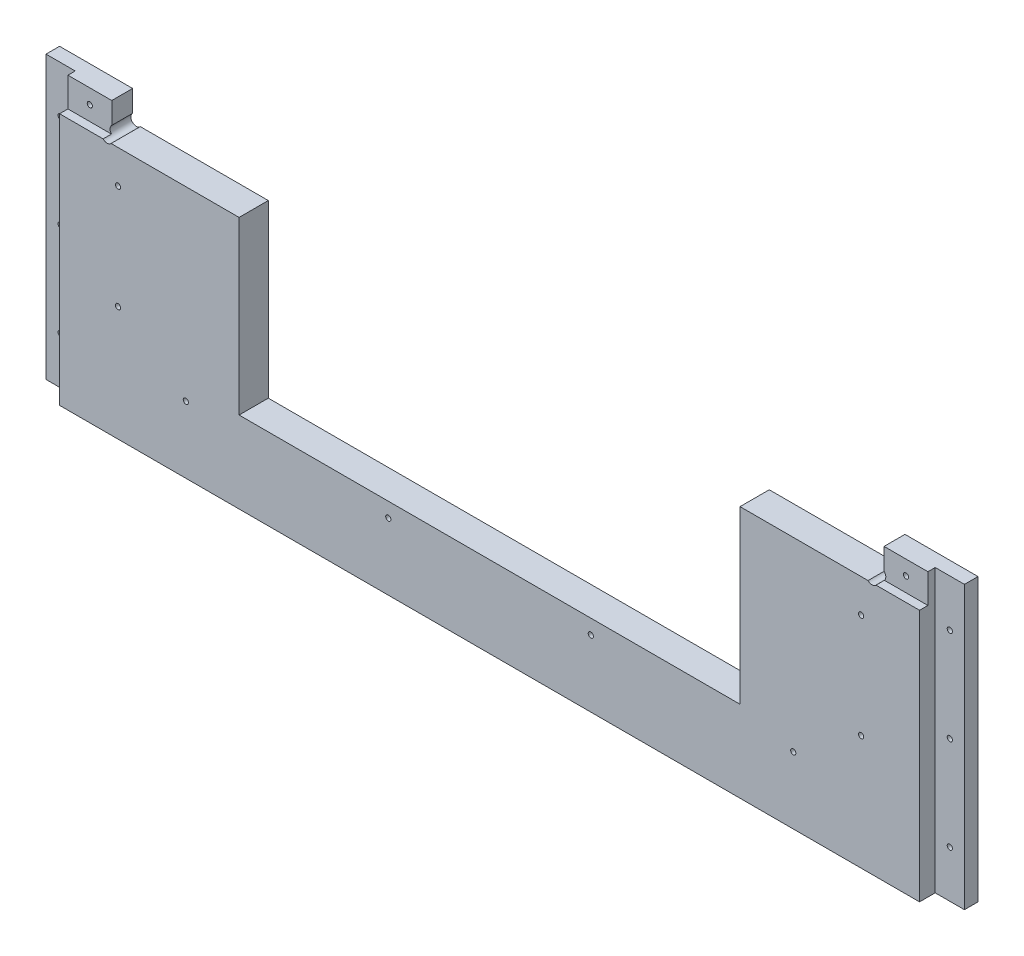
SolidWorks part; units mm, degrees
material "Pine"
ref_plane "Front Plane" through (0, 0, 0) normal (0, 0, 1) x (1, 0, 0)
ref_plane "Top Plane" through (0, 0, 0) normal (0, 1, 0) x (1, 0, 0)
ref_plane "Right Plane" through (0, 0, 0) normal (1, 0, 0) x (0, 0, -1)
sketch "Sketch1" plane through (0, 0, 0) normal (0, 0, 1) x (1, 0, 0)
  line L0 (8932.6508, -5243.5125) -> (10226.1458, -5243.5125)
  line L1 (9086.3208, -4722.0918) -> (10222.9708, -4853.7812)
  line L2 (8914.8708, -6342.0625) -> (10197.5708, -6342.0625)
  line L3 (8914.8708, -5808.6625) -> (10197.5708, -5808.6625)
  line L4 (8919.6333, -5253.0375) -> (10218.2083, -5253.0375)
  line L5 (9134.2633, -4656.1375) -> (9134.2633, -4638.3575)
  line L6 (9091.0833, -4638.3575) -> (9134.2633, -4638.3575)
  line L7 (9091.0833, -4567.2375) -> (9091.0833, -4638.3575)
  line L8 (9134.2633, -4656.1375) -> (9581.3033, -4656.1375)
  line L9 (9091.0833, -4567.2375) -> (9624.4833, -4567.2375)
  line L10 (9581.3033, -4656.1375) -> (9581.3033, -4638.3575)
  line L11 (9581.3033, -4638.3575) -> (9624.4833, -4638.3575)
  line L12 (9624.4833, -4567.2375) -> (9624.4833, -4638.3575)
  line L13 (8932.6508, -5225.7325) -> (9344.9775, -5225.7325)
  line L14 (8932.6508, -5256.2125) -> (8932.6508, -5243.5125)
  line L15 (8911.6958, -5256.2125) -> (8932.6508, -5256.2125)
  line L16 (8914.8708, -4722.0918) -> (9086.3208, -4722.0918)
  line L17 (8911.6958, -4715.5913) -> (8932.6508, -4715.5913)
  line L18 (8914.8708, -6342.0625) -> (8914.8708, -5808.6625)
  line L19 (12082.9917, -4722.0918) -> (10946.3417, -4853.7812)
  line L20 (12236.6617, -5243.5125) -> (10943.1667, -5243.5125)
  line L21 (10951.1042, -5253.0375) -> (12249.6792, -5253.0375)
  line L22 (10838.3917, -5656.2625) -> (11308.2917, -5656.2625)
  line L23 (10838.3917, -5719.7625) -> (11308.2917, -5719.7625)
  line L24 (10838.3917, -5742.5368) -> (11308.2917, -5742.5368)
  line L25 (10806.6417, -6342.0625) -> (11340.0417, -6342.0625)
  line L26 (10803.4667, -6335.7125) -> (11343.2167, -6335.7125)
  line L27 (10803.4667, -6317.9325) -> (11343.2167, -6317.9325)
  line L28 (10943.1667, -5225.7325) -> (11376.4483, -5225.7325)
  line L29 (11506.7292, -4754.5625) -> (10806.6417, -4827.5875)
  line L30 (11506.7292, -4567.2375) -> (11506.7292, -4754.5625)
  line L31 (10806.6417, -4567.2375) -> (10806.6417, -4827.5875)
  line L32 (10806.6417, -4567.2375) -> (11506.7292, -4567.2375)
  line L33 (10235.6708, -6329.3625) -> (10245.1958, -6329.3625)
  line L34 (10245.1958, -6329.3625) -> (10254.7208, -6278.5625)
  line L35 (10302.3458, -6329.3625) -> (10311.8708, -6278.5625)
  line L36 (10302.3458, -6329.3625) -> (10292.8208, -6329.3625)
  line L37 (10245.1958, -5821.3625) -> (10254.7208, -5872.1625)
  line L38 (10235.6708, -5821.3625) -> (10245.1958, -5821.3625)
  line L39 (10292.8208, -5821.3625) -> (10302.3458, -5821.3625)
  line L40 (10302.3458, -5821.3625) -> (10311.8708, -5872.1625)
  line L41 (10235.6708, -5821.3625) -> (10235.6708, -6329.3625)
  line L42 (10254.7208, -5872.1625) -> (10254.7208, -6278.5625)
  line L43 (10311.8708, -5872.1625) -> (10311.8708, -6278.5625)
  line L44 (10292.8208, -5821.3625) -> (10292.8208, -6329.3625)
  line L45 (8932.6508, -5225.7325) -> (8932.6508, -4715.5913)
  line L46 (8911.6958, -4715.5913) -> (8911.6958, -5256.2125)
  line L47 (8914.8708, -5248.275) -> (8914.8708, -4722.0918)
  line L48 (8919.6333, -5253.0375) -> (8914.8708, -5248.275)
  line L49 (8914.8708, -5145.0875) -> (8937.426, -5145.0875)
  line L50 (8914.8708, -5202.2375) -> (8937.426, -5202.2375)
  line L51 (10838.3917, -5656.2625) -> (10838.3917, -5719.7625)
  line L52 (10832.0417, -5736.1868) -> (10856.1717, -5736.1868)
  line L53 (10806.6417, -6342.0625) -> (10806.6417, -5818.7368)
  line L54 (10832.0417, -5649.9125) -> (10856.1717, -5649.9125)
  line L55 (10832.0417, -5726.1125) -> (10856.1717, -5726.1125)
  line L56 (10806.6417, -5818.7368) -> (10833.9015, -5818.7368)
  line L57 (10832.0417, -5806.0442) -> (10851.6815, -5806.0442)
  line L58 (10856.1717, -5801.5541) -> (10856.1717, -5736.1868)
  line L59 (10838.3917, -5814.2467) -> (10838.3917, -5742.5368)
  line L60 (10832.0417, -5806.0442) -> (10832.0417, -5736.1868)
  line L61 (10803.4667, -6317.9325) -> (10803.4667, -6335.7125)
  line L62 (10197.5708, -5808.6625) -> (10197.5708, -6342.0625)
  line L63 (9762.3842, -6348.4125) -> (9762.3842, -5802.3125)
  line L64 (9780.1642, -6348.4125) -> (9762.3842, -6348.4125)
  line L65 (9780.1642, -5802.3125) -> (9780.1642, -6348.4125)
  line L66 (9762.3842, -5802.3125) -> (9780.1642, -5802.3125)
  line L67 (9332.2775, -6348.4125) -> (9332.2775, -5802.3125)
  line L68 (9332.2775, -6348.4125) -> (9350.0575, -6348.4125)
  line L69 (9350.0575, -5802.3125) -> (9350.0575, -6348.4125)
  line L70 (9332.2775, -5802.3125) -> (9350.0575, -5802.3125)
  line L71 (9993.8374, -6061.075) -> (9993.8374, -6045.2418)
  line L72 (9998.5999, -6065.8375) -> (10014.4331, -6065.8375)
  line L73 (9998.5999, -6084.8875) -> (10014.4331, -6084.8875)
  line L74 (9993.8374, -6105.4832) -> (9993.8374, -6089.65)
  line L75 (9974.7874, -6105.4832) -> (9974.7874, -6089.65)
  line L76 (9954.1917, -6084.8875) -> (9970.0249, -6084.8875)
  line L77 (9974.7874, -6061.075) -> (9974.7874, -6045.2418)
  line L78 (9954.1917, -6065.8375) -> (9970.0249, -6065.8375)
  line L79 (10793.9417, -6237.2875) -> (10816.4969, -6237.2875)
  line L80 (10793.9417, -6294.4375) -> (10816.4969, -6294.4375)
  line L81 (10856.1717, -5649.9125) -> (10856.1717, -5726.1125)
  line L82 (10832.0417, -5726.1125) -> (10832.0417, -5649.9125)
  line L83 (10226.1458, -5225.7325) -> (10226.1458, -5243.5125)
  line L84 (10205.1908, -5257.8) -> (10205.1908, -4844.2499)
  line L85 (10230.9083, -4844.2499) -> (10230.9083, -5257.8)
  line L86 (10205.1908, -5257.8) -> (10230.9083, -5257.8)
  line L87 (10205.1908, -4844.2499) -> (10230.9083, -4844.2499)
  line L88 (10946.3417, -5176.8375) -> (10968.8969, -5176.8375)
  line L89 (9349.4676, -5141.9125) -> (9358.2674, -5141.9125)
  line L90 (10946.3417, -5119.6875) -> (10968.8969, -5119.6875)
  line L91 (9929.011, -4660.9635) -> (10066.0807, -4660.9635)
  line L92 (9929.011, -4678.7435) -> (10066.0807, -4678.7435)
  line L93 (10943.1667, -5225.7325) -> (10943.1667, -5243.5125)
  line L94 (10946.3417, -5248.275) -> (10951.1042, -5253.0375)
  line L95 (10946.3417, -5257.8063) -> (10946.3417, -4849.0188)
  line L96 (10964.1217, -5257.8) -> (10964.1217, -4844.2499)
  line L97 (10938.4042, -4844.2499) -> (10938.4042, -5257.8)
  line L98 (10938.4042, -5257.8) -> (10964.1217, -5257.8)
  line L99 (10964.1217, -4844.2499) -> (10938.4042, -4844.2499)
  line L100 (10344.8908, -4560.8875) -> (10369.0208, -4560.8875)
  line L101 (10344.8908, -4560.8875) -> (10369.0208, -4560.8875)
  line L102 (10800.2917, -4560.8875) -> (10824.4217, -4560.8875)
  line L103 (10200.4156, -5119.6875) -> (10222.9708, -5119.6875)
  line L104 (10200.4156, -5176.8375) -> (10222.9708, -5176.8375)
  line L105 (9344.9775, -5146.4026) -> (9344.9775, -5225.7325)
  line L106 (10344.8908, -4560.8875) -> (10344.8908, -4833.9375)
  line L107 (9792.8642, -5225.7325) -> (9792.8642, -5146.4026)
  line L108 (9362.7575, -5225.7325) -> (9775.0842, -5225.7325)
  line L109 (9680.3633, -4761.8396) -> (9680.3633, -4559.9604)
  line L110 (9656.2333, -4559.9604) -> (9680.3633, -4559.9604)
  line L111 (9656.2333, -4761.8396) -> (9680.3633, -4761.8396)
  line L112 (9656.2333, -4761.8396) -> (9656.2333, -4559.9604)
  line L113 (9779.5743, -5141.9125) -> (9788.374, -5141.9125)
  line L114 (10070.5708, -4665.4536) -> (10070.5708, -4674.2534)
  line L115 (9924.5208, -4674.2534) -> (9924.5208, -4665.4536)
  line L116 (12127.4417, -6188.3925) -> (12205.5015, -6188.3925)
  line L117 (12209.9917, -6170.6125) -> (12209.9917, -6183.9024)
  line L118 (9792.8642, -5225.7325) -> (10226.1458, -5225.7325)
  line L119 (9662.5833, -4754.5625) -> (10362.6708, -4827.5875)
  line L120 (9662.5833, -4567.2375) -> (9662.5833, -4754.5625)
  line L121 (10362.6708, -4567.2375) -> (10362.6708, -4827.5875)
  line L122 (9662.5833, -4567.2375) -> (10362.6708, -4567.2375)
  line L123 (10824.4217, -4833.9375) -> (10800.2917, -4833.9375)
  line L124 (10800.2917, -4833.9375) -> (10800.2917, -4560.8875)
  line L125 (10824.4217, -4560.8875) -> (10824.4217, -4833.9375)
  line L126 (10344.8908, -4833.9375) -> (10369.0208, -4833.9375)
  line L127 (10369.0208, -4833.9375) -> (10369.0208, -4560.8875)
  line L128 (10222.9708, -5248.275) -> (10218.2083, -5253.0375)
  line L129 (10222.9708, -5257.8063) -> (10222.9708, -4849.0188)
  line L130 (11734.6544, -5701.375) -> (11739.2301, -5701.375)
  line L131 (9362.7575, -5225.7325) -> (9362.7575, -5146.4026)
  line L132 (9775.0842, -5146.4026) -> (9775.0842, -5225.7325)
  line L133 (11761.3864, -5701.375) -> (11756.8282, -5701.375)
  line L134 (11734.6544, -5693.755) -> (11739.2301, -5693.755)
  line L135 (11761.4039, -5693.755) -> (11756.8282, -5693.755)
  line L136 (11734.6544, -5701.375) -> (11739.2301, -5701.375)
  line L137 (11744.3462, -5721.3024) -> (11744.3462, -5706.4179)
  line L138 (11751.7122, -5721.3024) -> (11751.7122, -5706.4179)
  line L139 (11740.0917, -6170.6125) -> (11740.0917, -6183.9024)
  line L140 (11689.2917, -6188.3925) -> (11822.6417, -6188.3925)
  line L141 (11689.2917, -6348.4093) -> (11689.2917, -6164.2657)
  line L142 (11689.2917, -6164.2657) -> (11746.4417, -6164.2657)
  line L143 (11746.4417, -6164.2657) -> (11746.4417, -6188.3925)
  line L144 (11689.2917, -6164.2657) -> (11746.4417, -6164.2657)
  line L145 (11340.0417, -5818.7368) -> (11340.0417, -6342.0625)
  line L146 (11290.5117, -5726.1125) -> (11314.6417, -5726.1125)
  line L147 (11290.5117, -5649.9125) -> (11290.5117, -5726.1125)
  line L148 (11340.0417, -5818.7368) -> (11312.7818, -5818.7368)
  line L149 (11314.6417, -5806.0442) -> (11295.0018, -5806.0442)
  line L150 (11290.5117, -5801.5541) -> (11290.5117, -5736.1868)
  line L151 (11308.2917, -5814.2467) -> (11308.2917, -5742.5368)
  line L152 (11314.6417, -5806.0442) -> (11314.6417, -5736.1868)
  line L153 (11290.5117, -5736.1868) -> (11314.6417, -5736.1868)
  line L154 (11848.0417, -6267.1325) -> (11962.3417, -6267.1325)
  line L155 (11962.3417, -6267.1325) -> (11962.3417, -6203.6325)
  line L156 (11343.2167, -6317.9325) -> (11343.2167, -6335.7125)
  line L157 (11365.4417, -5656.2625) -> (11365.4417, -5719.7625)
  line L158 (11365.4417, -5656.2625) -> (11479.7417, -5656.2625)
  line L159 (11778.1917, -6071.3937) -> (11802.3217, -6071.3937)
  line L160 (11314.6417, -5726.1125) -> (11314.6417, -5649.9125)
  line L161 (11314.6417, -5649.9125) -> (11290.5117, -5649.9125)
  line L162 (11308.2917, -5719.7625) -> (11308.2917, -5656.2625)
  line L163 (11689.2917, -6348.4093) -> (11713.4217, -6348.4093)
  line L164 (12203.6417, -6164.2657) -> (12260.7917, -6164.2657)
  line L165 (11713.4217, -6348.4093) -> (11713.4217, -6164.2657)
  line L166 (11695.6417, -6342.0625) -> (11695.6417, -6170.6125)
  line L167 (11695.6417, -6048.5337) -> (11699.4517, -6052.3437)
  line L168 (11822.6417, -6292.5325) -> (11822.6417, -6188.3925)
  line L169 (11695.6417, -6342.0625) -> (11695.6417, -6170.6125)
  line L170 (11848.0417, -6203.6325) -> (11962.3417, -6203.6325)
  line L171 (11848.0417, -6203.6325) -> (11848.0417, -6267.1325)
  line L172 (11987.7417, -6267.1325) -> (11987.7417, -6203.6325)
  line L173 (11784.5417, -6077.7437) -> (11784.5417, -6141.2438)
  line L174 (11517.8417, -5656.2625) -> (11632.1417, -5656.2625)
  line L175 (11632.1417, -5656.2625) -> (11632.1417, -5719.7625)
  line L176 (11632.1417, -5719.7625) -> (11517.8417, -5719.7625)
  line L177 (11517.8417, -5719.7625) -> (11517.8417, -5656.2625)
  line L178 (11692.4667, -6028.2137) -> (11692.4667, -6045.9937)
  line L179 (11695.6417, -5979.3188) -> (11718.1969, -5979.3188)
  line L180 (11695.6417, -5922.1687) -> (11718.1969, -5922.1687)
  line L181 (11821.0415, -5722.9375) -> (11821.0415, -5943.6)
  line L182 (11687.7042, -5651.5) -> (11701.9917, -5651.5)
  line L183 (11687.7042, -5651.5) -> (11687.7042, -6055.5251)
  line L184 (11687.7042, -6055.5251) -> (11701.9917, -6055.5251)
  line L185 (11701.9917, -6055.5251) -> (11701.9917, -5651.5)
  line L186 (11695.6417, -6055.2013) -> (11695.6417, -5649.595)
  line L187 (11695.6417, -5656.2625) -> (11695.6417, -6048.5337)
  line L188 (11695.6417, -6170.6125) -> (11740.0917, -6170.6125)
  line L189 (12203.6417, -6164.2657) -> (12203.6417, -6188.3925)
  line L190 (12254.4417, -6342.0625) -> (12254.4417, -6170.6125)
  line L191 (12129.0419, -5943.6) -> (12129.0419, -5722.9375)
  line L192 (12254.4417, -6048.5337) -> (12250.6317, -6052.3437)
  line L193 (12257.6167, -6045.9937) -> (12257.6167, -6028.2137)
  line L194 (12248.0917, -5651.5) -> (12262.3792, -5651.5)
  line L195 (12262.3792, -5651.5) -> (12262.3792, -6055.5251)
  line L196 (12262.3792, -6055.5251) -> (12248.0917, -6055.5251)
  line L197 (12248.0917, -6055.5251) -> (12248.0917, -5651.5)
  line L198 (12254.4417, -6141.2438) -> (12254.4417, -6077.7437)
  line L199 (12236.6617, -6164.2657) -> (12260.7917, -6164.2657)
  line L200 (12102.0417, -6267.1325) -> (11987.7417, -6267.1325)
  line L201 (11330.1865, -6237.2875) -> (11352.7417, -6237.2875)
  line L202 (11330.1865, -6294.4375) -> (11352.7417, -6294.4375)
  line L203 (11474.6617, -5851.8425) -> (11492.4417, -5851.8425)
  line L204 (11474.6617, -5808.6625) -> (11474.6617, -5851.8425)
  line L205 (11403.5417, -5808.6625) -> (11474.6617, -5808.6625)
  line L206 (11492.4417, -5851.8425) -> (11492.4417, -6298.8825)
  line L207 (11403.5417, -6342.0625) -> (11403.5417, -5808.6625)
  line L208 (11474.6617, -6298.8825) -> (11492.4417, -6298.8825)
  line L209 (11474.6617, -6342.0625) -> (11474.6617, -6298.8825)
  line L210 (11403.5417, -6342.0625) -> (11474.6617, -6342.0625)
  line L211 (11619.4417, -5851.8425) -> (11601.6617, -5851.8425)
  line L212 (11601.6617, -5808.6625) -> (11601.6617, -5851.8425)
  line L213 (11530.5417, -5808.6625) -> (11601.6617, -5808.6625)
  line L214 (11619.4417, -5851.8425) -> (11619.4417, -6298.8825)
  line L215 (11530.5417, -6342.0625) -> (11530.5417, -5808.6625)
  line L216 (11619.4417, -6298.8825) -> (11601.6617, -6298.8825)
  line L217 (11601.6617, -6342.0625) -> (11601.6617, -6298.8825)
  line L218 (11530.5417, -6342.0625) -> (11601.6617, -6342.0625)
  line L219 (11479.7417, -5719.7625) -> (11479.7417, -5656.2625)
  line L220 (11365.4417, -5719.7625) -> (11479.7417, -5719.7625)
  line L221 (11778.1917, -6147.5937) -> (11802.3217, -6147.5937)
  line L222 (11802.3217, -6071.3937) -> (11802.3217, -6147.5937)
  line L223 (11778.1917, -6147.5937) -> (11778.1917, -6071.3937)
  line L224 (12254.4417, -5922.1687) -> (12231.8865, -5922.1687)
  line L225 (12254.4417, -5979.3188) -> (12231.8865, -5979.3188)
  line L226 (12254.4417, -6055.2013) -> (12254.4417, -5649.595)
  line L227 (12254.4417, -6048.5337) -> (12254.4417, -5656.2625)
  line L228 (11841.6917, -5702.2873) -> (12108.3917, -5702.2873)
  line L229 (11822.6417, -6292.5325) -> (12127.4417, -6292.5325)
  line L230 (12127.4417, -6292.5325) -> (12127.4417, -6188.3925)
  line L231 (12254.4417, -6170.6125) -> (12209.9917, -6170.6125)
  line L232 (11695.6417, -6342.0625) -> (12254.4417, -6342.0625)
  line L233 (12236.6617, -6348.4093) -> (12260.7917, -6348.4093)
  line L234 (12260.7917, -6348.4093) -> (12260.7917, -6164.2657)
  line L235 (12236.6617, -6348.4093) -> (12236.6617, -6164.2657)
  line L236 (12102.0417, -6203.6325) -> (12102.0417, -6267.1325)
  line L237 (11987.7417, -6203.6325) -> (12102.0417, -6203.6325)
  line L238 (12236.6617, -6147.5937) -> (12236.6617, -6071.3937)
  line L239 (12203.6417, -6188.3925) -> (12260.7917, -6188.3925)
  line L240 (11098.7417, -4665.4536) -> (11098.7417, -4674.2534)
  line L241 (11394.2283, -5146.4026) -> (11394.2283, -5225.7325)
  line L242 (11376.4483, -5225.7325) -> (11376.4483, -5146.4026)
  line L243 (11394.2283, -5225.7325) -> (11806.555, -5225.7325)
  line L244 (11841.6917, -5964.2502) -> (12108.3917, -5964.2502)
  line L245 (12236.6617, -6147.5937) -> (12260.7917, -6147.5937)
  line L246 (12236.6617, -5256.2125) -> (12236.6617, -5243.5125)
  line L247 (12260.7917, -6147.5937) -> (12260.7917, -6071.3937)
  line L248 (12260.7917, -6071.3937) -> (12236.6617, -6071.3937)
  line L249 (12254.4417, -6077.7437) -> (11784.5417, -6077.7437)
  line L250 (11784.5417, -6141.2438) -> (12254.4417, -6141.2438)
  line L252 (12254.4417, -5656.2625) -> (11695.6417, -5656.2625)
  line L253 (11699.4517, -6052.3437) -> (12250.6317, -6052.3437)
  line L254 (11692.4667, -6045.9937) -> (12257.6167, -6045.9937)
  line L255 (11692.4667, -6028.2137) -> (12257.6167, -6028.2137)
  line L256 (11824.335, -5146.4026) -> (11824.335, -5225.7325)
  line L257 (11811.0451, -5141.9125) -> (11819.8449, -5141.9125)
  line L258 (11244.7917, -4674.2534) -> (11244.7917, -4665.4536)
  line L259 (11806.555, -5225.7325) -> (11806.555, -5146.4026)
  line L260 (11488.9492, -4761.8396) -> (11488.9492, -4559.9604)
  line L261 (11488.9492, -4559.9604) -> (11513.0792, -4559.9604)
  line L262 (11488.9492, -4761.8396) -> (11513.0792, -4761.8396)
  line L263 (11513.0792, -4761.8396) -> (11513.0792, -4559.9604)
  line L264 (11240.3015, -4660.9635) -> (11103.2318, -4660.9635)
  line L265 (11103.2318, -4678.7435) -> (11240.3015, -4678.7435)
  line L266 (12236.6617, -5225.7325) -> (12236.6617, -4715.5913)
  line L267 (12257.6167, -4715.5913) -> (12257.6167, -5256.2125)
  line L268 (12254.4417, -5248.275) -> (12254.4417, -4722.0918)
  line L269 (12236.6617, -5225.7325) -> (11824.335, -5225.7325)
  line L270 (12035.0492, -4656.1375) -> (12035.0492, -4638.3575)
  line L271 (12078.2292, -4638.3575) -> (12035.0492, -4638.3575)
  line L272 (12078.2292, -4567.2375) -> (12078.2292, -4638.3575)
  line L273 (12035.0492, -4656.1375) -> (11588.0092, -4656.1375)
  line L274 (11544.8292, -4567.2375) -> (12078.2292, -4567.2375)
  line L275 (11588.0092, -4656.1375) -> (11588.0092, -4638.3575)
  line L276 (11544.8292, -4638.3575) -> (11588.0092, -4638.3575)
  line L277 (11544.8292, -4567.2375) -> (11544.8292, -4638.3575)
  line L278 (12249.6792, -5253.0375) -> (12254.4417, -5248.275)
  line L280 (12257.6167, -5256.2125) -> (12236.6617, -5256.2125)
  line L281 (12231.8865, -5145.0875) -> (12254.4417, -5145.0875)
  line L282 (12231.8865, -5202.2375) -> (12254.4417, -5202.2375)
  line L283 (12236.6617, -4715.5913) -> (12257.6167, -4715.5913)
  line L284 (12082.9917, -4722.0918) -> (12254.4417, -4722.0918)
  line L285 (11380.9385, -5141.9125) -> (11389.7382, -5141.9125)
  circle A0 centre (8923.7608, -4778.9042) radius 1.5875
  circle A1 centre (9062.6598, -4736.3765) radius 2.3685
  circle A2 centre (9051.3958, -6281.7375) radius 22.225
  circle A3 centre (9083.1458, -6249.9875) radius 1.5875
  circle A4 centre (9083.1458, -6313.4875) radius 1.5875
  circle A5 centre (9019.6458, -6249.9875) radius 1.5875
  circle A6 centre (9019.6458, -6313.4875) radius 1.5875
  circle A7 centre (8972.3383, -5202.2375) radius 1.5875
  circle A8 centre (8923.7608, -5015.9708) radius 1.5875
  circle A9 centre (8923.7608, -5134.5042) radius 1.5875
  circle A10 centre (9054.5708, -5234.6225) radius 1.5875
  circle A11 centre (8923.7608, -4897.4375) radius 1.5875
  circle A12 centre (8972.3383, -5087.9375) radius 1.5875
  circle A13 centre (8972.3383, -5145.0875) radius 1.5875
  circle A14 centre (10847.2817, -5668.9625) radius 1.5875
  circle A15 centre (10847.2817, -5707.0625) radius 1.5875
  circle A16 centre (10847.2817, -5755.2368) radius 1.5875
  circle A17 centre (10851.4092, -6237.2875) radius 1.5875
  circle A18 centre (10851.4092, -6294.4375) radius 1.5875
  circle A19 centre (10847.2817, -5793.3442) radius 1.5875
  arc A20 (10833.9015, -5818.7368) -> (10838.3917, -5814.2467) centre (10836.1466, -5816.4918) ccw
  arc A21 (10851.6815, -5806.0442) -> (10856.1717, -5801.5541) centre (10853.9266, -5803.7992) ccw
  circle A22 centre (10882.8417, -6040.4375) radius 1.5875
  circle A23 centre (10882.8417, -6218.2375) radius 1.5875
  circle A24 centre (10882.8417, -5862.6375) radius 1.5875
  circle A25 centre (10908.2417, -6326.8225) radius 1.5875
  circle A26 centre (10908.2417, -6326.8225) radius 1.5875
  circle A27 centre (10851.4092, -6180.1375) radius 1.5875
  circle A28 centre (10815.5317, -4783.4231) radius 1.5875
  circle A29 centre (10815.5317, -4696.9488) radius 1.5875
  circle A30 centre (10815.5317, -4610.4746) radius 1.5875
  circle A31 centre (10979.1323, -4867.0082) radius 2.3685
  circle A32 centre (10190.1802, -4867.0082) radius 2.3685
  circle A33 centre (10955.2317, -4929.9812) radius 1.5875
  circle A34 centre (10955.2317, -5031.5812) radius 1.5875
  circle A35 centre (10214.0808, -4929.9812) radius 1.5875
  circle A36 centre (10214.0808, -5031.5812) radius 1.5875
  circle A37 centre (9341.1675, -6265.8625) radius 1.5875
  circle A38 centre (9771.2742, -5884.8625) radius 1.5875
  circle A39 centre (9771.2742, -6138.8625) radius 1.5875
  circle A40 centre (9771.2742, -6011.8625) radius 1.5875
  arc A41 (10036.2287, -6113.8083) -> (10051.3426, -6111.6033) centre (10042.9639, -6107.0732) ccw
  arc A42 (10051.3426, -6111.6033) -> (10051.3426, -6039.1217) centre (9984.3124, -6075.3625) ccw
  arc A43 (10051.3426, -6039.1217) -> (10036.2287, -6036.9167) centre (10042.9639, -6043.6518) ccw
  arc A44 (10034.5851, -6102.5431) -> (10034.5851, -6048.1819) centre (9984.3124, -6075.3625) ccw
  arc A45 (10034.5851, -6102.5431) -> (10036.2287, -6113.8083) centre (10042.9639, -6107.0732) ccw
  arc A46 (10036.2287, -6036.9167) -> (10034.5851, -6048.1819) centre (10042.9639, -6043.6518) ccw
  arc A47 (9945.8666, -6127.2787) -> (9948.0717, -6142.3927) centre (9952.6018, -6134.0139) ccw
  arc A48 (9948.0717, -6142.3927) -> (10020.5532, -6142.3927) centre (9984.3124, -6075.3625) ccw
  arc A49 (10020.5532, -6142.3927) -> (10022.7583, -6127.2787) centre (10016.0231, -6134.0139) ccw
  arc A50 (9957.1319, -6125.6352) -> (10011.493, -6125.6352) centre (9984.3124, -6075.3625) ccw
  arc A51 (9957.1319, -6125.6352) -> (9945.8666, -6127.2787) centre (9952.6018, -6134.0139) ccw
  arc A52 (10022.7583, -6127.2787) -> (10011.493, -6125.6352) centre (10016.0231, -6134.0139) ccw
  arc A53 (9932.3962, -6036.9167) -> (9917.2822, -6039.1217) centre (9925.661, -6043.6518) ccw
  arc A54 (9917.2822, -6039.1217) -> (9917.2822, -6111.6033) centre (9984.3124, -6075.3625) ccw
  arc A55 (9917.2822, -6111.6033) -> (9932.3962, -6113.8083) centre (9925.661, -6107.0732) ccw
  arc A56 (9934.0398, -6048.1819) -> (9934.0398, -6102.5431) centre (9984.3124, -6075.3625) ccw
  arc A57 (9934.0398, -6048.1819) -> (9932.3962, -6036.9167) centre (9925.661, -6043.6518) ccw
  arc A58 (9932.3962, -6113.8083) -> (9934.0398, -6102.5431) centre (9925.661, -6107.0732) ccw
  arc A59 (9945.8666, -6023.4463) -> (9957.1319, -6025.0898) centre (9952.6018, -6016.7111) ccw
  arc A60 (10011.493, -6025.0898) -> (10022.7583, -6023.4463) centre (10016.0231, -6016.7111) ccw
  arc A61 (10011.493, -6025.0898) -> (9957.1319, -6025.0898) centre (9984.3124, -6075.3625) ccw
  arc A62 (9948.0717, -6008.3323) -> (9945.8666, -6023.4463) centre (9952.6018, -6016.7111) ccw
  arc A63 (10020.5532, -6008.3323) -> (9948.0717, -6008.3323) centre (9984.3124, -6075.3625) ccw
  arc A64 (10022.7583, -6023.4463) -> (10020.5532, -6008.3323) centre (10016.0231, -6016.7111) ccw
  arc A65 (10005.0943, -6187.7574) -> (10096.7073, -6096.1443) centre (9984.3124, -6075.3625) ccw
  arc A66 (9993.8374, -6178.3911) -> (10005.0943, -6187.7574) centre (10003.3624, -6178.3911) ccw
  arc A67 (10001.6306, -6169.0249) -> (10077.9748, -6092.6807) centre (9984.3124, -6075.3625) ccw
  arc A68 (10087.3411, -6084.8875) -> (10077.9748, -6092.6807) centre (10087.3411, -6094.4125) ccw
  arc A69 (10001.6306, -6169.0249) -> (9993.8374, -6178.3911) centre (10003.3624, -6178.3911) ccw
  arc A70 (9963.5306, -6187.7574) -> (9974.7874, -6178.3911) centre (9965.2624, -6178.3911) ccw
  arc A71 (9871.9176, -6096.1443) -> (9963.5306, -6187.7574) centre (9984.3124, -6075.3625) ccw
  arc A72 (9881.2838, -6084.8875) -> (9871.9176, -6096.1443) centre (9881.2838, -6094.4125) ccw
  arc A73 (9890.65, -6092.6807) -> (9966.9943, -6169.0249) centre (9984.3124, -6075.3625) ccw
  arc A74 (9974.7874, -6178.3911) -> (9966.9943, -6169.0249) centre (9965.2624, -6178.3911) ccw
  arc A75 (9890.65, -6092.6807) -> (9881.2838, -6084.8875) centre (9881.2838, -6094.4125) ccw
  arc A76 (9871.9176, -6054.5807) -> (9881.2838, -6065.8375) centre (9881.2838, -6056.3125) ccw
  arc A77 (9963.5306, -5962.9676) -> (9871.9176, -6054.5807) centre (9984.3124, -6075.3625) ccw
  arc A78 (9974.7874, -5972.3339) -> (9963.5306, -5962.9676) centre (9965.2624, -5972.3339) ccw
  arc A79 (9966.9943, -5981.7001) -> (9890.65, -6058.0443) centre (9984.3124, -6075.3625) ccw
  arc A80 (9881.2838, -6065.8375) -> (9890.65, -6058.0443) centre (9881.2838, -6056.3125) ccw
  arc A81 (9966.9943, -5981.7001) -> (9974.7874, -5972.3339) centre (9965.2624, -5972.3339) ccw
  arc A82 (10077.9748, -6058.0443) -> (10087.3411, -6065.8375) centre (10087.3411, -6056.3125) ccw
  arc A83 (9993.8374, -5972.3339) -> (10001.6306, -5981.7001) centre (10003.3624, -5972.3339) ccw
  arc A84 (10077.9748, -6058.0443) -> (10001.6306, -5981.7001) centre (9984.3124, -6075.3625) ccw
  arc A85 (10087.3411, -6065.8375) -> (10096.7073, -6054.5807) centre (10087.3411, -6056.3125) ccw
  arc A86 (10096.7073, -6054.5807) -> (10005.0943, -5962.9676) centre (9984.3124, -6075.3625) ccw
  arc A87 (10005.0943, -5962.9676) -> (9993.8374, -5972.3339) centre (10003.3624, -5972.3339) ccw
  arc A88 (10014.4331, -6065.8375) -> (10018.7361, -6059.0339) centre (10014.4331, -6061.075) ccw
  arc A89 (10018.7361, -6059.0339) -> (10000.641, -6040.9388) centre (9984.3124, -6075.3625) ccw
  arc A90 (10000.641, -6040.9388) -> (9993.8374, -6045.2418) centre (9998.5999, -6045.2418) ccw
  arc A91 (9993.8374, -6061.075) -> (9998.5999, -6065.8375) centre (9998.5999, -6061.075) ccw
  arc A92 (9993.8374, -6105.4832) -> (10000.641, -6109.7862) centre (9998.5999, -6105.4832) ccw
  arc A93 (10000.641, -6109.7862) -> (10018.7361, -6091.6911) centre (9984.3124, -6075.3625) ccw
  arc A94 (10018.7361, -6091.6911) -> (10014.4331, -6084.8875) centre (10014.4331, -6089.65) ccw
  arc A95 (9998.5999, -6084.8875) -> (9993.8374, -6089.65) centre (9998.5999, -6089.65) ccw
  arc A96 (9954.1917, -6084.8875) -> (9949.8888, -6091.6911) centre (9954.1917, -6089.65) ccw
  arc A97 (9949.8888, -6091.6911) -> (9967.9839, -6109.7862) centre (9984.3124, -6075.3625) ccw
  arc A98 (9967.9839, -6109.7862) -> (9974.7874, -6105.4832) centre (9970.0249, -6105.4832) ccw
  arc A99 (9974.7874, -6089.65) -> (9970.0249, -6084.8875) centre (9970.0249, -6089.65) ccw
  arc A100 (9970.0249, -6065.8375) -> (9974.7874, -6061.075) centre (9970.0249, -6061.075) ccw
  arc A101 (9949.8888, -6059.0339) -> (9954.1917, -6065.8375) centre (9954.1917, -6061.075) ccw
  arc A102 (9967.9839, -6040.9388) -> (9949.8888, -6059.0339) centre (9984.3124, -6075.3625) ccw
  arc A103 (9974.7874, -6045.2418) -> (9967.9839, -6040.9388) centre (9970.0249, -6045.2418) ccw
  arc A104 (10096.7073, -6096.1443) -> (10087.3411, -6084.8875) centre (10087.3411, -6094.4125) ccw
  circle A105 centre (9771.2742, -6265.8625) radius 1.5875
  circle A106 centre (9341.1675, -5884.8625) radius 1.5875
  circle A107 centre (9341.1675, -6138.8625) radius 1.5875
  circle A108 centre (9341.1675, -6011.8625) radius 1.5875
  circle A109 centre (11037.2315, -4887.5494) radius 15.0812
  arc A110 (9349.4676, -5141.9125) -> (9344.9775, -5146.4026) centre (9347.2226, -5144.1576) ccw
  arc A111 (9362.7575, -5146.4026) -> (9358.2674, -5141.9125) centre (9360.5124, -5144.1576) ccw
  circle A112 centre (9946.7458, -4669.8535) radius 1.5875
  arc A113 (9924.5208, -4674.2534) -> (9929.011, -4678.7435) centre (9926.7659, -4676.4984) ccw
  circle A114 centre (11003.8092, -5176.8375) radius 1.5875
  circle A115 centre (11003.8092, -5119.6875) radius 1.5875
  circle A116 centre (10353.7808, -4696.9488) radius 1.5875
  circle A117 centre (10353.7808, -4610.4746) radius 1.5875
  circle A118 centre (10353.7808, -4783.4231) radius 1.5875
  circle A119 centre (11003.8092, -5062.5375) radius 1.5875
  circle A120 centre (9353.8675, -5160.9625) radius 1.5875
  circle A121 centre (9638.7708, -5234.6225) radius 1.5875
  circle A122 centre (9671.4733, -4724.1144) radius 1.5875
  circle A123 centre (9671.4733, -4661.3637) radius 1.5875
  circle A124 centre (9671.4733, -4598.6129) radius 1.5875
  arc A125 (9792.8642, -5146.4026) -> (9788.374, -5141.9125) centre (9790.6191, -5144.1576) ccw
  arc A126 (9779.5743, -5141.9125) -> (9775.0842, -5146.4026) centre (9777.3292, -5144.1576) ccw
  circle A127 centre (10048.3458, -4669.8535) radius 1.5875
  arc A128 (10070.5708, -4665.4536) -> (10066.0807, -4660.9635) centre (10068.3258, -4663.2086) ccw
  arc A129 (10066.0807, -4678.7435) -> (10070.5708, -4674.2534) centre (10068.3258, -4676.4984) ccw
  circle A130 centre (9997.5458, -4669.8535) radius 1.5875
  arc A131 (9929.011, -4660.9635) -> (9924.5208, -4665.4536) centre (9926.7659, -4663.2086) ccw
  circle A132 centre (10132.081, -4887.5494) radius 15.0812
  circle A133 centre (10165.5033, -5176.8375) radius 1.5875
  circle A134 centre (10165.5033, -5119.6875) radius 1.5875
  circle A135 centre (9486.3708, -5234.6225) radius 1.5875
  circle A136 centre (10165.5033, -5062.5375) radius 1.5875
  circle A137 centre (9206.9708, -5234.6225) radius 1.5875
  circle A138 centre (10070.5708, -5234.6225) radius 1.5875
  circle A139 centre (9918.1708, -5234.6225) radius 1.5875
  circle A140 centre (9783.9742, -5160.9625) radius 1.5875
  circle A141 centre (9783.9742, -5193.9825) radius 1.5875
  circle A142 centre (9353.8675, -5193.9825) radius 1.5875
  circle A143 centre (11073.3417, -6326.8225) radius 1.5875
  circle A144 centre (11073.3417, -6326.8225) radius 1.5875
  circle A145 centre (11295.2742, -6180.1375) radius 1.5875
  circle A146 centre (11295.2742, -6294.4375) radius 1.5875
  circle A147 centre (11295.2742, -6237.2875) radius 1.5875
  circle A148 centre (11975.0417, -5692.775) radius 3.4925
  circle A149 centre (11263.8417, -5862.6375) radius 1.5875
  arc A150 (11739.2301, -5701.375) -> (11744.3462, -5706.4179) centre (11748.0292, -5697.565) ccw
  arc A151 (11751.7122, -5706.4179) -> (11756.8282, -5701.375) centre (11748.0292, -5697.565) ccw
  arc A152 (11744.3462, -5721.3024) -> (11751.7122, -5721.3024) centre (11748.0292, -5725.505) ccw
  arc A153 (11734.6544, -5693.755) -> (11724.9787, -5697.565) centre (11730.5667, -5697.565) ccw
  arc A154 (11756.8282, -5693.755) -> (11739.2301, -5693.755) centre (11748.0292, -5697.565) ccw
  arc A155 (11724.9787, -5697.565) -> (11734.6544, -5701.375) centre (11730.5667, -5697.565) ccw
  arc A156 (11761.3864, -5701.375) -> (11771.0797, -5697.565) centre (11765.4842, -5697.565) ccw
  arc A157 (11771.0797, -5697.565) -> (11761.4039, -5693.755) centre (11765.4917, -5697.565) ccw
  arc A158 (11740.0917, -6183.9024) -> (11744.5818, -6188.3925) centre (11742.3367, -6186.1474) ccw
  arc A159 (12205.5015, -6188.3925) -> (12209.9917, -6183.9024) centre (12207.7466, -6186.1474) ccw
  circle A160 centre (11299.4017, -5793.3442) radius 1.5875
  arc A161 (11308.2917, -5814.2467) -> (11312.7818, -5818.7368) centre (11310.5367, -5816.4918) ccw
  arc A162 (11290.5117, -5801.5541) -> (11295.0018, -5806.0442) centre (11292.7567, -5803.7992) ccw
  circle A163 centre (11704.5317, -6314.149) radius 1.5875
  circle A164 centre (11748.9817, -6208.7125) radius 1.5875
  circle A165 centre (11263.8417, -6218.2375) radius 1.5875
  circle A166 centre (11263.8417, -6040.4375) radius 1.5875
  circle A167 centre (11238.4417, -6326.8225) radius 1.5875
  circle A168 centre (11238.4417, -6326.8225) radius 1.5875
  circle A169 centre (11299.4017, -5668.9625) radius 1.5875
  circle A170 centre (11299.4017, -5707.0625) radius 1.5875
  circle A171 centre (11726.7567, -6179.5025) radius 1.5875
  circle A172 centre (11704.5317, -6199.3198) radius 1.5875
  circle A173 centre (11748.9817, -6272.2125) radius 1.5875
  circle A174 centre (11704.5317, -6256.7344) radius 1.5875
  circle A175 centre (11299.4017, -5755.2368) radius 1.5875
  circle A176 centre (11913.4467, -6301.4225) radius 1.5875
  circle A177 centre (11790.2567, -6301.4225) radius 1.5875
  circle A178 centre (11793.4317, -6128.5437) radius 1.5875
  circle A179 centre (11753.1092, -5865.0188) radius 1.5875
  circle A180 centre (11809.9417, -6037.1038) radius 1.5875
  circle A181 centre (11809.9417, -6037.1038) radius 1.5875
  circle A182 centre (11753.1092, -5922.1687) radius 1.5875
  circle A183 centre (11975.0417, -5973.7625) radius 3.4925
  circle A184 centre (11975.0417, -6037.1038) radius 1.5875
  circle A185 centre (11753.1092, -5979.3188) radius 1.5875
  circle A186 centre (11975.0417, -6037.1038) radius 1.5875
  arc A187 (11841.6917, -5702.2873) -> (11821.0415, -5722.9375) centre (11841.6917, -5722.9375) ccw
  circle A188 centre (11811.5292, -5833.2687) radius 3.4925
  arc A189 (11821.0415, -5943.6) -> (11841.6917, -5964.2502) centre (11841.6917, -5943.6) ccw
  circle A190 centre (12196.9742, -5865.0188) radius 1.5875
  arc A191 (12129.0419, -5722.9375) -> (12108.3917, -5702.2873) centre (12108.3917, -5722.9375) ccw
  circle A192 centre (12036.6367, -6301.4225) radius 1.5875
  circle A193 centre (12159.8267, -6301.4225) radius 1.5875
  circle A194 centre (12138.5542, -5833.2687) radius 3.4925
  circle A195 centre (12197.2917, -5761.0375) radius 15.0812
  circle A196 centre (11793.4317, -6090.4437) radius 1.5875
  circle A197 centre (12196.9742, -5922.1687) radius 1.5875
  arc A198 (12108.3917, -5964.2502) -> (12129.0419, -5943.6) centre (12108.3917, -5943.6) ccw
  circle A199 centre (12196.9742, -5979.3188) radius 1.5875
  circle A200 centre (12201.1017, -6272.2125) radius 1.5875
  circle A201 centre (12245.5517, -6314.149) radius 1.5875
  circle A202 centre (12245.5517, -6256.7344) radius 1.5875
  circle A203 centre (12201.1017, -6208.7125) radius 1.5875
  circle A204 centre (12223.3267, -6179.5025) radius 1.5875
  circle A205 centre (12245.5517, -6199.3198) radius 1.5875
  circle A206 centre (11171.7667, -4669.8535) radius 1.5875
  circle A207 centre (11222.5667, -4669.8535) radius 1.5875
  arc A208 (11240.3015, -4678.7435) -> (11244.7917, -4674.2534) centre (11242.5466, -4676.4984) ccw
  circle A209 centre (11385.3383, -5193.9825) radius 1.5875
  circle A210 centre (12106.6527, -4736.3765) radius 2.3685
  circle A211 centre (12140.1417, -6037.1038) radius 1.5875
  circle A212 centre (12140.1417, -6037.1038) radius 1.5875
  circle A213 centre (12245.5517, -6090.4437) radius 1.5875
  circle A214 centre (12245.5517, -6128.5437) radius 1.5875
  circle A215 centre (11385.3383, -5160.9625) radius 1.5875
  arc A216 (11824.335, -5146.4026) -> (11819.8449, -5141.9125) centre (11822.0899, -5144.1576) ccw
  arc A217 (11811.0451, -5141.9125) -> (11806.555, -5146.4026) centre (11808.8001, -5144.1576) ccw
  circle A218 centre (11815.445, -5193.9825) radius 1.5875
  circle A219 centre (11815.445, -5160.9625) radius 1.5875
  circle A220 centre (11530.5417, -5234.6225) radius 1.5875
  circle A221 centre (11962.3417, -5234.6225) radius 1.5875
  arc A222 (11244.7917, -4665.4536) -> (11240.3015, -4660.9635) centre (11242.5466, -4663.2086) ccw
  circle A223 centre (11682.9417, -5234.6225) radius 1.5875
  circle A224 centre (11497.8392, -4724.1144) radius 1.5875
  circle A225 centre (11497.8392, -4661.3637) radius 1.5875
  circle A226 centre (11497.8392, -4598.6129) radius 1.5875
  circle A227 centre (11120.9667, -4669.8535) radius 1.5875
  arc A228 (11103.2318, -4660.9635) -> (11098.7417, -4665.4536) centre (11100.9867, -4663.2086) ccw
  arc A229 (11098.7417, -4674.2534) -> (11103.2318, -4678.7435) centre (11100.9867, -4676.4984) ccw
  circle A230 centre (12196.9742, -5202.2375) radius 1.5875
  circle A231 centre (12245.5517, -5015.9708) radius 1.5875
  circle A232 centre (12245.5517, -5134.5042) radius 1.5875
  circle A233 centre (12114.7417, -5234.6225) radius 1.5875
  circle A234 centre (12245.5517, -4897.4375) radius 1.5875
  circle A235 centre (12245.5517, -4778.9042) radius 1.5875
  circle A236 centre (12196.9742, -5087.9375) radius 1.5875
  circle A237 centre (12196.9742, -5145.0875) radius 1.5875
  circle A238 centre (11098.7417, -5234.6225) radius 1.5875
  circle A239 centre (11251.1417, -5234.6225) radius 1.5875
  arc A240 (11380.9385, -5141.9125) -> (11376.4483, -5146.4026) centre (11378.6934, -5144.1576) ccw
  arc A241 (11394.2283, -5146.4026) -> (11389.7382, -5141.9125) centre (11391.9833, -5144.1576) ccw
sketch "Sketch2" plane through (0, 0, 0) normal (0, 0, 1) x (1, 0, 0)
  line L0 (12254.4417, -6342.0625) -> (12254.4417, -6170.6125)
  line L1 (12254.4417, -6170.6125) -> (12209.9917, -6170.6125)
  line L2 (12209.9917, -6170.6125) -> (12209.9917, -6188.3925)
  line L3 (12209.9917, -6188.3925) -> (12127.4417, -6188.3925)
  line L4 (12127.4417, -6188.3925) -> (12127.4417, -6292.5325)
  line L5 (12127.4417, -6292.5325) -> (11822.6417, -6292.5325)
  line L6 (11822.6417, -6292.5325) -> (11822.6417, -6188.3925)
  line L7 (11822.6417, -6188.3925) -> (11740.0917, -6188.3925)
  line L8 (11740.0917, -6188.3925) -> (11740.0917, -6170.6125)
  line L9 (11740.0917, -6170.6125) -> (11695.6417, -6170.6125)
  line L10 (11695.6417, -6170.6125) -> (11695.6417, -6342.0625)
  line L11 (11695.6417, -6342.0625) -> (12254.4417, -6342.0625)
  dimension "D1" = 17.78
  dimension "D2" = 104.14
  dimension "D4" = 558.8
extrude "Extrude1" add sketch "Sketch2" against normal blind 17.78
sketch "Sketch3" plane through (0, 0, 0) normal (0, 0, 1) x (1, 0, 0)
  line L0 (11740.0917, -6188.3925) -> (11740.0917, -6170.6125)
  line L1 (11740.0917, -6170.6125) -> (11695.6417, -6170.6125)
  line L2 (11695.6417, -6170.6125) -> (11695.6417, -6188.3925)
  line L3 (11695.6417, -6188.3925) -> (11740.0917, -6188.3925)
  line L4 (12209.9917, -6170.6125) -> (12254.4417, -6170.6125)
  line L5 (12254.4417, -6170.6125) -> (12254.4417, -6188.3925)
  line L6 (12254.4417, -6188.3925) -> (12209.9917, -6188.3925)
  line L7 (12209.9917, -6188.3925) -> (12209.9917, -6170.6125)
  line L8 (11695.6417, -6170.6125) -> (11695.6417, -6342.0625) construction
  line L9 (12254.4417, -6342.0625) -> (12254.4417, -6170.6125) construction
  line L10 (12209.9917, -6170.6125) -> (12209.9917, -6188.3925) construction
  line L11 (12209.9917, -6188.3925) -> (12127.4417, -6188.3925) construction
extrude "Cut-Extrude1" cut sketch "Sketch3" against normal blind 5.08
sketch "Sketch4" plane through (0, 0, 0) normal (0, 0, 1) x (1, 0, 0)
  line L0 (11695.6417, -6342.0625) -> (11713.4217, -6342.0625)
  line L1 (11713.4217, -6342.0625) -> (11713.4217, -6170.6125)
  line L2 (11713.4217, -6170.6125) -> (11695.6417, -6170.6125)
  line L3 (11695.6417, -6170.6125) -> (11695.6417, -6342.0625)
  line L4 (12236.6617, -6342.0625) -> (12254.4417, -6342.0625)
  line L5 (12254.4417, -6342.0625) -> (12254.4417, -6170.6125)
  line L6 (12254.4417, -6170.6125) -> (12236.6617, -6170.6125)
  line L7 (12236.6617, -6170.6125) -> (12236.6617, -6342.0625)
  line L8 (11695.6417, -6342.0625) -> (12254.4417, -6342.0625) construction
  line L9 (11695.6417, -6170.6125) -> (11740.0917, -6170.6125) construction
  line L10 (12254.4417, -6170.6125) -> (12209.9917, -6170.6125) construction
  dimension "D1" = 17.78
  dimension "D2" = 17.78
extrude "Cut-Extrude2" cut sketch "Sketch4" against normal blind 9.525
sketch "Sketch5" plane through (0, 0, 0) normal (0, 0, 1) x (1, 0, 0)
  line L0 (11740.0917, -6188.3925) -> (11742.3367, -6186.1474) construction
  line L1 (11822.6417, -6188.3925) -> (11713.4217, -6188.3925) construction
  line L2 (12209.9917, -6188.3925) -> (12207.7466, -6186.1474) construction
  line L3 (12236.6617, -6188.3925) -> (12127.4417, -6188.3925) construction
  line L4 (11913.4467, -6301.4225) -> (12036.6367, -6301.4225) construction
  line L5 (11790.2567, -6301.4225) -> (11913.4467, -6301.4225) construction
  line L6 (12036.6367, -6301.4225) -> (12159.8267, -6301.4225) construction
  line L7 (11975.0417, -6292.5325) -> (11975.0417, -6301.4225) construction
  line L8 (11695.6417, -6256.3375) -> (11713.4217, -6256.3375) construction
  line L9 (12127.4417, -6292.5325) -> (11822.6417, -6292.5325) construction
  line L10 (11748.9817, -6208.7125) -> (11748.9817, -6272.2125) construction
  line L11 (11748.9817, -6240.4625) -> (11822.6417, -6240.4625) construction
  line L12 (11822.6417, -6292.5325) -> (11822.6417, -6188.3925) construction
  line L13 (12201.1017, -6208.7125) -> (12201.1017, -6272.2125) construction
  line L14 (12223.3267, -6188.3925) -> (12223.3267, -6170.6125) construction
  line L15 (12201.1017, -6240.4625) -> (12127.4417, -6240.4625) construction
  line L16 (12127.4417, -6188.3925) -> (12127.4417, -6292.5325) construction
  line L17 (12209.9917, -6188.3925) -> (12236.6617, -6188.3925) construction
  line L18 (12236.6617, -6170.6125) -> (12209.9917, -6170.6125) construction
  line L19 (11726.7567, -6188.3925) -> (11726.7567, -6170.6125) construction
  line L20 (11695.6417, -6170.6125) -> (11695.6417, -6342.0625) construction
  line L21 (11713.4217, -6188.3925) -> (11740.0917, -6188.3925) construction
  line L22 (11740.0917, -6170.6125) -> (11713.4217, -6170.6125) construction
  line L23 (12254.4417, -6256.3375) -> (12236.6617, -6256.3375) construction
  line L24 (12254.4417, -6342.0625) -> (12254.4417, -6170.6125) construction
  line L25 (12236.6617, -6170.6125) -> (12236.6617, -6342.0625) construction
  line L26 (12245.5517, -6313.4875) -> (12245.5517, -6256.3375) construction
  line L27 (12245.5517, -6256.3375) -> (12245.5517, -6199.1875) construction
  line L28 (11713.4217, -6342.0625) -> (11713.4217, -6170.6125) construction
  line L29 (11704.5317, -6313.4875) -> (11704.5317, -6256.3375) construction
  line L30 (11704.5317, -6256.3375) -> (11704.5317, -6199.1875) construction
  circle A0 centre (11704.5317, -6313.4875) radius 1.5875
  circle A1 centre (11704.5317, -6256.3375) radius 1.5875
  circle A2 centre (11704.5317, -6199.1875) radius 1.5875
  circle A3 centre (11726.7567, -6179.5025) radius 1.5875
  circle A4 centre (11748.9817, -6208.7125) radius 1.5875
  circle A5 centre (11748.9817, -6272.2125) radius 1.5875
  circle A6 centre (11790.2567, -6301.4225) radius 1.5875
  circle A7 centre (11913.4467, -6301.4225) radius 1.5875
  circle A8 centre (12036.6367, -6301.4225) radius 1.5875
  circle A9 centre (12159.8267, -6301.4225) radius 1.5875
  circle A10 centre (12245.5517, -6313.4875) radius 1.5875
  circle A11 centre (12245.5517, -6256.3375) radius 1.5875
  circle A12 centre (12201.1017, -6272.2125) radius 1.5875
  circle A13 centre (12201.1017, -6208.7125) radius 1.5875
  circle A14 centre (12245.5517, -6199.1875) radius 1.5875
  circle A15 centre (12223.3267, -6179.5025) radius 1.5875
  circle A16 centre (11742.3367, -6186.1474) radius 3.302
  circle A17 centre (12207.7466, -6186.1474) radius 3.302
  dimension "D1" = 45
  dimension "D5" = 8.89
  dimension "D2" = 3.175
  dimension "D3" = 45
  dimension "D4" = 3.175
  dimension "D6" = 123.19
  dimension "D7" = 63.5
  dimension "D8" = 73.66
  dimension "D9" = 63.5
  dimension "D10" = 73.66
  dimension "D11" = 57.15
  dimension "D12" = 57.15
  dimension "D13" = 57.15
  dimension "D14" = 57.15
extrude "Cut-Extrude3" cut sketch "Sketch5" against normal up to surface (17.78 mm away) up to face at (11975.0417, -6225.4342, -17.78)
